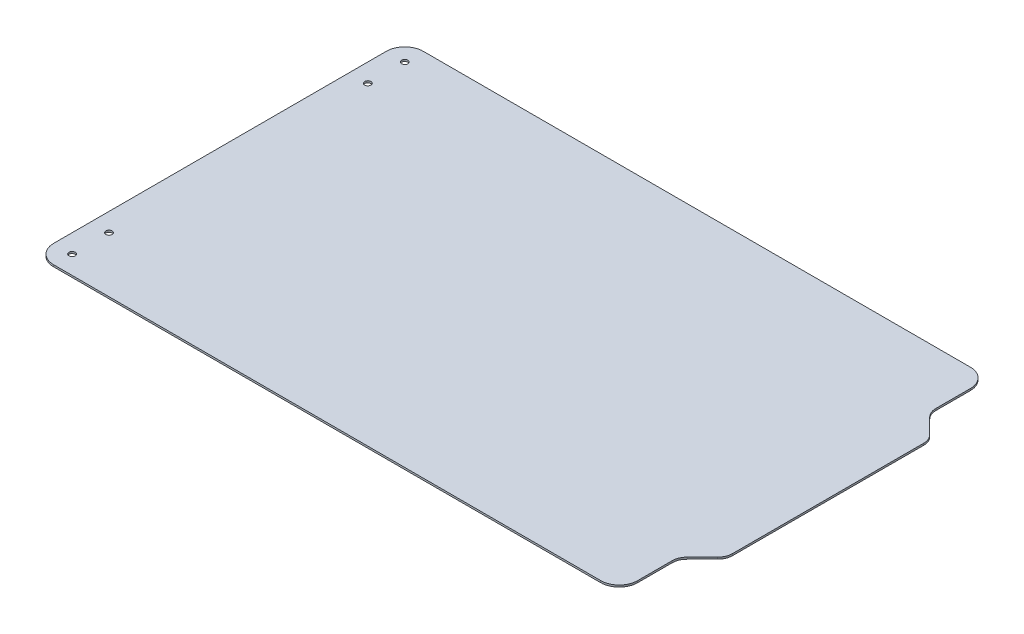
SolidWorks part; units mm, degrees
material "AISI 1020 Steel, Cold Rolled"
ref_plane "Front Plane" through (0, 0, 0) normal (0, 0, 1) x (1, 0, 0)
ref_plane "Top Plane" through (0, 0, 0) normal (0, 1, 0) x (1, 0, 0)
ref_plane "Right Plane" through (0, 0, 0) normal (1, 0, 0) x (0, 0, -1)
sketch "Sketch1" plane through (0, 0, 0) normal (0, 1, 0) x (1, 0, 0)
  line L1 (-164.5, 100) -> (164.5, 100)
  line L2 (-164.5, 100) -> (-164.5, -100)
  line L3 (-164.5, -100) -> (164.5, -100)
  line L4 (164.5, 100) -> (164.5, -100)
  line L5 (-164.5, 100) -> (164.5, -100) construction
  line L6 (-164.5, -100) -> (164.5, 100) construction
  point P0 (0, 0)
  dimension "D1" = 329
  dimension "D2" = 200
extrude "Boss-Extrude1" add sketch "Sketch1" along normal blind 1
sketch "Sketch2" plane through (0, 0, 0) normal (0, -1, 0) x (-1, 0, 0)
  line L0 (-164.5, -55) -> (-151.5, -68)
  line L5 (-164.5, -100) -> (-164.5, 100) construction
  line L6 (-151.5, -68) -> (-151.5, -100)
  line L7 (164.5, -100) -> (-164.5, -100) construction
  line L8 (-151.5, -100) -> (-164.5, -100)
  line L9 (-164.5, -100) -> (-164.5, -55)
  line L10 (-0.55, 0) -> (0.55, 0) construction
  line L11 (-151.5, 100) -> (-164.5, 100)
  line L12 (-151.5, 68) -> (-151.5, 100)
  line L13 (-164.5, 55) -> (-151.5, 68)
  line L14 (-164.5, 100) -> (-164.5, 55)
  dimension "D1" = 13
  dimension "D2" = 45
  dimension "D3" = 32
extrude "Cut-Extrude1" cut sketch "Sketch2" against normal through all
fillet "Fillet1" radius 8 4 edges at (151.5, 0.5, -68) (164.5, 0.5, -55) (151.5, 0.5, 68) (164.5, 0.5, 55)
fillet "Fillet2" radius 10 4 edges at (151.5, 0.5, -100) (-164.5, 0.5, -100) (-164.5, 0.5, 100) (151.5, 0.5, 100)
sketch "Sketch3" plane through (0, 0, 0) normal (0, -1, 0) x (1, 0, 0)
  circle A0 centre (-154.5, -70) radius 1.7 construction
  circle A1 centre (-154.5, -90) radius 1.7 construction
  circle A2 centre (-154.5, 70) radius 1.7 construction
  circle A3 centre (-154.5, 90) radius 1.7 construction
  circle A4 centre (-154.5, -70) radius 1.7
  circle A5 centre (-154.5, -90) radius 1.7
  circle A6 centre (-154.5, 70) radius 1.7
  circle A7 centre (-154.5, 90) radius 1.7
extrude "Cut-Extrude2" cut sketch "Sketch3" against normal through all
